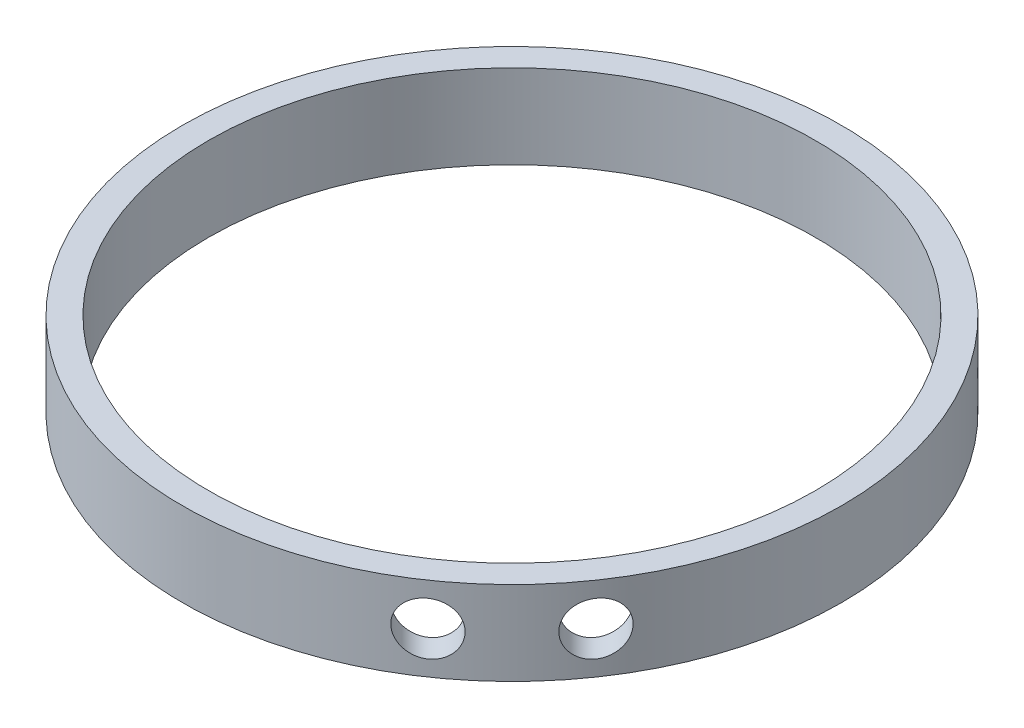
SolidWorks part; units mm, degrees
material "ABS"
ref_plane "Front Plane" through (0, 0, 0) normal (0, 0, 1) x (1, 0, 0)
ref_plane "Top Plane" through (0, 0, 0) normal (0, 1, 0) x (1, 0, 0)
ref_plane "Right Plane" through (0, 0, 0) normal (1, 0, 0) x (0, 0, -1)
sketch "Sketch1" plane through (0, 0, 0) normal (0, 0, 1) x (1, 0, 0)
  line L0 (0, 138.9318) -> (0, -74.0157) construction
  line L1 (44.45, 0) -> (44.45, 204.47)
  line L2 (44.45, 204.47) -> (50.6984, 204.47)
  line L3 (50.6984, 204.47) -> (50.6984, 108.966)
  line L4 (50.6984, 108.966) -> (52.832, 108.966)
  line L5 (52.832, 108.966) -> (52.832, 95.504)
  line L6 (52.832, 95.504) -> (50.6984, 95.504)
  line L7 (50.6984, 95.504) -> (50.6984, 0)
  line L8 (50.6984, 0) -> (44.45, 0)
  dimension "D1" = 88.9
  dimension "D2" = 204.47
  dimension "D3" = 13.462
  dimension "D4" = 101.3968
  dimension "D5" = 105.664
revolve "Revolve1" add sketch "Sketch1" angle 360 about L0
sketch "Sketch2" plane through (0, 204.47, 0) normal (0, 1, 0) x (1, 0, 0)
  circle A0 centre (0, 40.7035) radius 3.7465
  circle A1 centre (0, 0) radius 44.45 construction
  circle A2 centre (0, 40.7035) radius 7.9375
  circle A3 centre (0, 0) radius 50.8 construction
  point P26 (0, 0)
  dimension "D1" = 7.493
  dimension "D2" = 15.875
extrude "Boss-Extrude1" add sketch "Sketch2" against normal up to surface (204.47 mm away) up to face at (-50.6984, 0, 0)
fillet "Fillet1" radius 3.81 2 edges at (7.2879, 102.235, -43.8485) (-7.2879, 102.235, -43.8485)
pattern_circular "CirPattern1" count 4 over 360 about axis through (0, 138.9318, 0) along (0, 1, 0) of "Fillet1", "Boss-Extrude1" reverse direction yes
sketch "Sketch3" plane through (0, 204.47, 0) normal (0, 1, 0) x (1, 0, 0)
  circle A1 centre (0, 40.7035) radius 8.636
  dimension "D1" = 17.272
extrude "Cut-Extrude1" cut sketch "Sketch3" against normal blind 12.7
pattern_circular "CirPattern2" count 4 over 360 about axis through (0, 138.9318, 0) along (0, 1, 0) of "Cut-Extrude1" reverse direction yes
fillet "Fillet2" radius 2.54 8 edges at (-8.6158, 198.12, -41.2943) (8.6158, 198.12, -41.2943) (41.2943, 198.12, -8.6158) (41.2943, 198.12, 8.6158) (8.6158, 198.12, 41.2943) (-8.6158, 198.12, 41.2943) (-41.2943, 198.12, 8.6158) (-41.2943, 198.12, -8.6158)
ref_plane "Plane1" through (0, 102.235, 0) normal (0, 1, 0) x (1, 0, 0)
mirror "Mirror1" about plane through (0, 102.235, 0) normal (0, 1, 0) of "CirPattern2"
fillet "Fillet3" radius 2.54 8 edges at (-41.2943, 6.35, -8.6158) (-41.2943, 6.35, 8.6158) (8.6158, 6.35, 41.2943) (-8.6158, 6.35, 41.2943) (41.2943, 6.35, -8.6158) (41.2943, 6.35, 8.6158) (-8.6158, 6.35, -41.2943) (8.6158, 6.35, -41.2943)
chamfer "Chamfer1" [suppressed] distance 1.27 angle 80
ref_plane "Plane2" through (37.3579, 0, 37.3579) normal (0.7071, 0, 0.7071) x (0, 1, 0)
hole_wizard "5/16 Clearance Hole1" positions "Sketch6" profile "Sketch5" hole size "5/16" standard "ANSI Inch"
sketch "Sketch6" plane through (37.3579, 0, 37.3579) normal (0.7071, 0, 0.7071) x (0, 1, 0)
  line L1 (95.504, 0) -> (108.966, 0)
  line L3 (108.966, -50.6984) -> (108.966, 50.6984) construction
  line L5 (102.235, 9.525) -> (102.235, -9.525)
  line L7 (95.504, 52.832) -> (95.504, -52.832) construction
  point P0 (102.235, -9.525)
  point P2 (102.235, 9.525)
  point P36 (102.235, 0)
  point P40 (102.235, 0)
  dimension "D1" = 19.05
sketch "Sketch5" plane through (44.0931, 102.235, 30.6227) normal (0, 1, 0) x (0.7071, 0, -0.7071)
  line L0 (0, 0) -> (0, 57.3975)
  line L1 (0, 57.3975) -> (4.2164, 54.864)
  line L2 (4.2164, 54.864) -> (4.2164, 0)
  line L5 (4.2164, 0) -> (0, 0)
  line L10 (0, 57.3975) -> (-4.2164, 54.864) construction
  line L11 (0, -6.35) -> (0, 107.95) construction
  dimension "Hole Dia." = 8.4328
  dimension "Hole Depth" = 54.864
  dimension "Drill Angle" = 118
ref_plane "Plane3" through (37.3579, 0, -37.3579) normal (0.7071, 0, -0.7071) x (0, 1, 0)
hole_wizard "#6 Clearance Hole1" positions "Sketch7" profile "Sketch8" hole size "#6" standard "ANSI Inch"
sketch "Sketch7" plane through (37.3579, 0, -37.3579) normal (0.7071, 0, -0.7071) x (0, 1, 0)
  line L2 (95.504, 0) -> (108.966, 0)
  line L4 (108.966, -52.832) -> (108.966, 52.832) construction
  line L5 (95.504, 50.6984) -> (95.504, -50.6984) construction
  point P0 (102.235, 0)
  point P21 (102.235, 0)
sketch "Sketch8" plane through (37.3579, 102.235, -37.3579) normal (0, 1, 0) x (-0.7071, 0, -0.7071)
  line L0 (0, 0) -> (0, 56.0048)
  line L1 (0, 56.0048) -> (1.8986, 54.864)
  line L2 (1.8986, 54.864) -> (1.8986, 0)
  line L5 (1.8986, 0) -> (0, 0)
  line L10 (0, 56.0048) -> (-1.8987, 54.864) construction
  line L11 (0, -6.35) -> (0, 107.95) construction
  dimension "Hole Dia." = 3.7973
  dimension "Hole Depth" = 54.864
  dimension "Drill Angle" = 118
pattern_circular "CirPattern3" [suppressed] count 3 every 90 of bodies 108
sketch "Sketch9" plane through (0, 204.47, 0) normal (0, 1, 0) x (1, 0, 0)
  circle A0 centre (0, 0) radius 52.832
extrude "Cut-Extrude2" cut sketch "Sketch9" along normal up to surface (-108.966 mm away) from surface up to face at (-52.832, 95.504, 0) starting at face at (0, 0, 0)
sketch "Sketch10" plane through (0, 0, 0) normal (0, 0, 1) x (1, 0, 0)
  line L0 (0, 204.47) -> (0, 95.504) construction
  line L1 (50.6984, 204.47) -> (-50.6984, 204.47) construction
  line L2 (-52.832, 95.504) -> (52.832, 95.504) construction
  line L4 (52.832, 108.966) -> (48.387, 108.966)
  line L5 (52.832, 108.966) -> (52.832, 95.504)
  line L6 (52.832, 95.504) -> (48.387, 95.504)
  line L7 (48.387, 108.966) -> (48.387, 95.504)
  dimension "D1" = 4.445
revolve "Cut-Revolve1" [suppressed] cut sketch "Sketch10" angle 360 about L0
sketch "Sketch11" plane through (0, 0, 0) normal (0, 0, 1) x (1, 0, 0)
  line L0 (-52.832, 95.504) -> (52.832, 95.504) construction
  line L1 (48.641, 95.504) -> (0, 95.504)
  line L2 (48.641, 95.504) -> (48.641, 108.966)
  line L5 (50.6984, 204.47) -> (-50.6984, 204.47) construction
  line L6 (50.6984, 204.47) -> (0, 204.47)
  line L7 (50.6984, 204.47) -> (50.6984, 108.966)
  line L8 (50.6984, 108.966) -> (48.641, 108.966)
  line L10 (0, 95.504) -> (0, 204.47)
  line L11 (50.6984, 108.966) -> (-50.6984, 108.966) construction
  line L12 (7.9239, 204.47) -> (-7.9239, 204.47) construction
  dimension "D1" = 50.6984
  dimension "D2" = 48.641
revolve "Cut-Revolve2" cut sketch "Sketch11" angle 360 about L10
